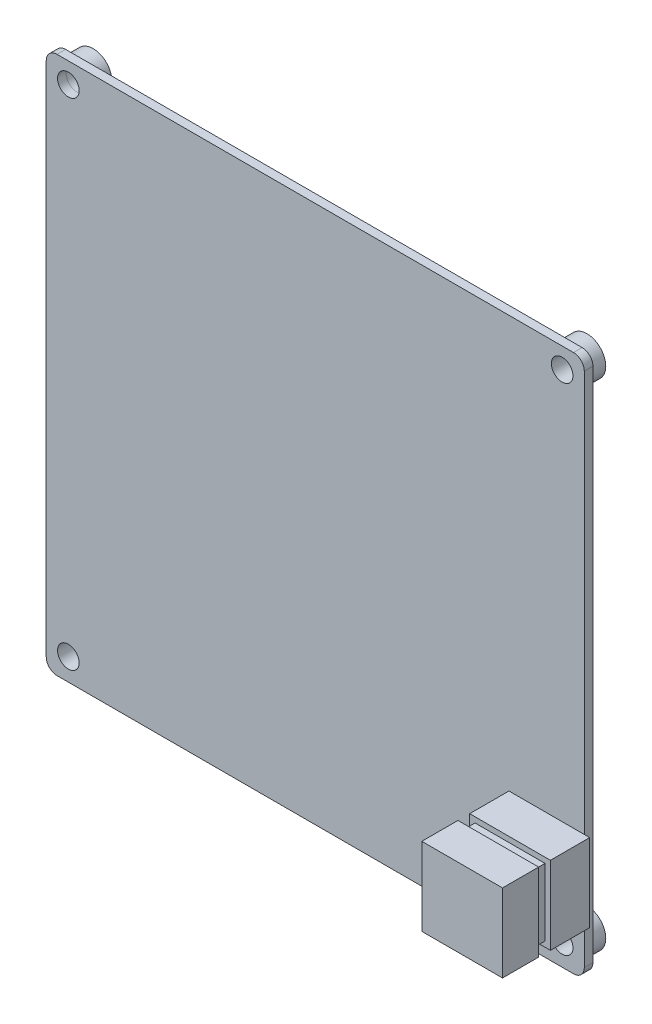
SolidWorks part; units mm, degrees
ref_plane "前视基准面" through (0, 0, 0) normal (0, 0, 1) x (1, 0, 0)
ref_plane "上视基准面" through (0, 0, 0) normal (0, 1, 0) x (1, 0, 0)
ref_plane "右视基准面" through (0, 0, 0) normal (1, 0, 0) x (0, 0, -1)
sketch "草图2" plane through (0, 0, 0) normal (0, 0, 1) x (1, 0, 0)
  line L9 (-50, -48) -> (-50, 48)
  line L14 (-48, 50) -> (48, 50)
  line L16 (50, -48) -> (50, 48)
  line L18 (-48, -50) -> (48, -50)
  arc A0 (-50, 48) -> (-48, 50) centre (-48, 48) cw
  arc A1 (50, 48) -> (48, 50) centre (48, 48) ccw
  arc A2 (50, -48) -> (48, -50) centre (48, -48) cw
  arc A3 (-50, -48) -> (-48, -50) centre (-48, -48) ccw
  circle A6 centre (-45.89, -45.89) radius 2.0065
  circle A7 centre (45.89, -45.89) radius 2.0065
  circle A8 centre (-45.89, 46.19) radius 2.0065
  circle A9 centre (45.89, 46.19) radius 2.0065
  point P16 (50, 0)
  point P20 (-50, 0)
extrude "凸台-拉伸1" add sketch "草图2" along normal blind 1.6
ref_plane "基准面4" through (50, 0, 0) normal (1, 0, 0) x (0, 0, -1)
sketch "草图3" plane through (50, 0, 0) normal (1, 0, 0) x (0, 0, -1)
  line L0 (-8.9, -33.82) -> (-8.9, -26.57)
  line L2 (-1.6, -41.07) -> (-1.6, -26.57)
  line L3 (-8.9, -33.82) -> (-8.9, -41.07)
  line L4 (-8.9, -41.07) -> (-1.6, -41.07)
  line L5 (-1.6, -26.57) -> (-8.9, -26.57)
  line L7 (-11.08, -26.57) -> (-11.08, -41.07)
  line L9 (-17.8, -41.07) -> (-11.08, -41.07)
  line L10 (-17.8, -41.07) -> (-17.8, -26.57)
  line L11 (-17.8, -26.57) -> (-11.08, -26.57)
extrude "凸台-拉伸2" add sketch "草图3" against normal blind 14 and the other way blind 1
sketch "草图4" plane through (50, 0, 0) normal (1, 0, 0) x (0, 0, -1)
  line L1 (-8.9, -26.57) -> (-8.9, -41.07) construction
  line L3 (-11.08, -41.07) -> (-11.08, -26.57) construction
  line L4 (-8.9, -40.07) -> (-11.08, -40.07)
  line L5 (-8.9, -40.07) -> (-8.9, -27.57)
  line L6 (-8.9, -27.57) -> (-11.08, -27.57)
  line L7 (-11.08, -40.07) -> (-11.08, -27.57)
extrude "凸台-拉伸3" add sketch "草图4" against normal blind 13
sketch "草图5" plane through (0, 0, 0) normal (0, 0, 1) x (1, 0, 0)
  circle A0 centre (-45.89, -45.89) radius 2.0065
  circle A1 centre (-45.89, -45.89) radius 3.5
  circle A2 centre (-45.89, 46.19) radius 2.0073
  circle A3 centre (-45.89, 46.19) radius 3.5
  circle A4 centre (45.89, 46.19) radius 2.0065
  circle A5 centre (45.89, 46.19) radius 3.5
  circle A6 centre (45.89, -45.89) radius 2.0065
  circle A7 centre (45.89, -45.89) radius 3.5
extrude "凸台-拉伸4" add sketch "草图5" against normal blind 3
